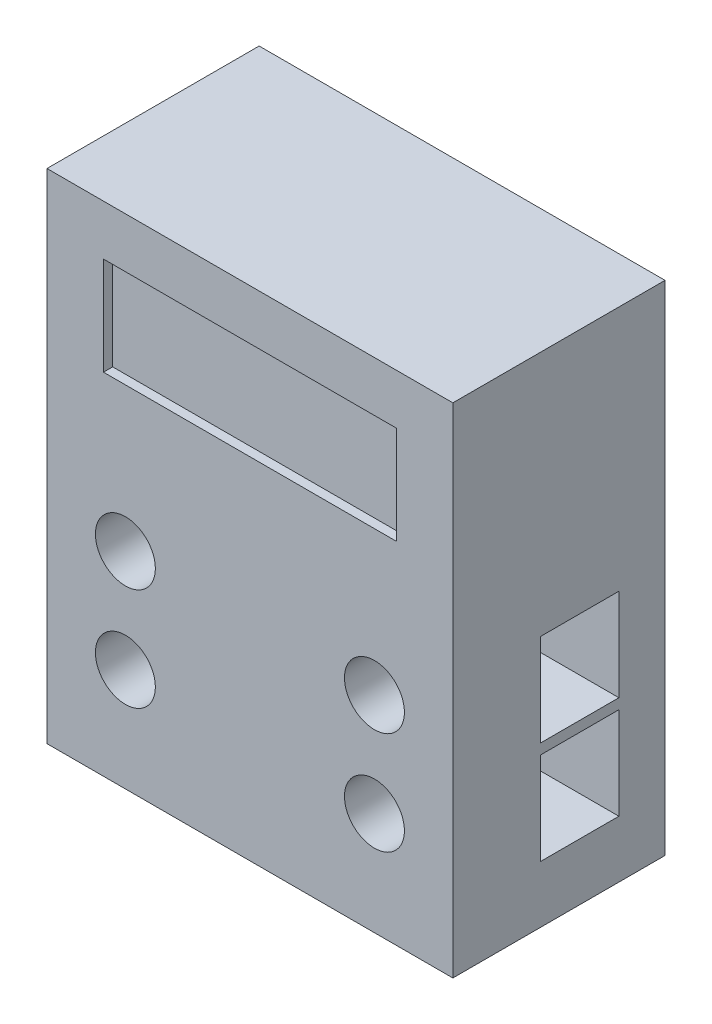
SolidWorks part; units mm, degrees
ref_plane "Front Plane" through (0, 0, 0) normal (0, 0, 1) x (1, 0, 0)
ref_plane "Top Plane" through (0, 0, 0) normal (0, 1, 0) x (1, 0, 0)
ref_plane "Right Plane" through (0, 0, 0) normal (1, 0, 0) x (0, 0, -1)
sketch "Sketch2" plane through (0, 0, 0) normal (0, 0, 1) x (1, 0, 0)
  line L0 (0, 32.5) -> (0, 0) construction
  line L1 (43.9999, -54) -> (-43.9999, -54)
  line L2 (43.9999, -54) -> (43.9999, 54)
  line L3 (43.9999, 54) -> (-43.9999, 54)
  line L4 (-43.9999, -54) -> (-43.9999, 54)
  line L5 (43.9999, -54) -> (-43.9999, 54) construction
  line L6 (43.9999, 54) -> (-43.9999, -54) construction
  line L9 (0, 0) -> (0, -20.5) construction
  line L10 (-31.75, 43.125) -> (31.75, 43.125)
  line L11 (-31.75, 43.125) -> (-31.75, 21.875)
  line L12 (-31.75, 21.875) -> (31.75, 21.875)
  line L13 (31.75, 43.125) -> (31.75, 21.875)
  line L14 (-31.75, 43.125) -> (31.75, 21.875) construction
  line L15 (-31.75, 21.875) -> (31.75, 43.125) construction
  line L16 (27, -31.625) -> (-27, -31.625)
  line L17 (27, -31.625) -> (27, -9.375)
  line L18 (27, -9.375) -> (-27, -9.375)
  line L19 (-27, -31.625) -> (-27, -9.375)
  line L20 (27, -31.625) -> (-27, -9.375) construction
  line L21 (27, -9.375) -> (-27, -31.625) construction
  circle A0 centre (-27, -9.375) radius 6.5
  circle A1 centre (27, -9.375) radius 6.5
  circle A2 centre (27, -31.625) radius 6.5
  circle A3 centre (-27, -31.625) radius 6.5
  point P0 (0, 0)
  point P5 (0, 32.5)
  point P8 (0, 0)
  point P26 (0, -20.5)
  dimension "D4" = 13
  dimension "D1" = 108
  dimension "D2" = 21.25
  dimension "D3" = 63.5
  dimension "D5" = 22.25
  dimension "D6" = 54
  dimension "D7" = 87.9997
  dimension "D8" = 32.5
  dimension "D9" = 20.5
extrude "Boss-Extrude1" add sketch "Sketch2" against normal blind 46 contours L4 L1 L2 L3 A3 L19 A0 L18 A1 L17 A2 L16 L10 L13 L12 L11 | A3 L16 A2 L17 A1 L18 A0 L19 region at (0, -1.6874, 0) region at (0, -20.5, 0)
sketch "Sketch3" plane through (0, 0, 0) normal (1, 0, 0) x (0, 0, -1)
  line L0 (46, -54) -> (0, -54) construction
  line L1 (46, 54) -> (0.0001, 54)
  line L2 (46, 54) -> (46, -54)
  line L3 (46, -54) -> (0.0001, -54)
  line L4 (0.0001, 54) -> (0.0001, -54)
  line L5 (46, 54) -> (0.0001, -54) construction
  line L6 (46, -54) -> (0.0001, 54) construction
  line L7 (46, -54) -> (46, 54) construction
  line L8 (23, -15.875) -> (23, -25.125) construction
  line L9 (30.5308, -2.875) -> (30.5308, -15.875) construction
  line L18 (34, 0.625) -> (34, -19.375)
  line L19 (34, -9.375) -> (27.5, -9.375) construction
  line L20 (36, -19.375) -> (34, -19.375)
  line L21 (36, 0.625) -> (36, -19.375)
  line L22 (36, 0.625) -> (34, 0.625)
  line L23 (34, -19.375) -> (34, 0.625)
  line L24 (19, 0.625) -> (34, 0.625)
  line L25 (19, -19.375) -> (19, 0.625)
  line L26 (19, -19.375) -> (34, -19.375)
  line L27 (46, -2.875) -> (0, -2.875) construction
  line L28 (0, -15.875) -> (46, -15.875) construction
  line L29 (46, -25.125) -> (0, -25.125) construction
  line L30 (0.0001, -20.5) -> (46, -20.5) construction
  line L31 (34, -31.625) -> (27.5, -31.625) construction
  line L32 (30.5308, -38.125) -> (30.5308, -25.125) construction
  line L33 (19, -21.625) -> (34, -21.625)
  line L34 (19, -21.625) -> (19, -41.625)
  line L35 (19, -41.625) -> (34, -41.625)
  line L36 (34, -21.625) -> (34, -41.625)
  line L37 (36, -41.625) -> (34, -41.625)
  line L38 (36, -41.625) -> (36, -21.625)
  line L39 (36, -21.625) -> (34, -21.625)
  line L40 (34, -41.625) -> (34, -21.625)
  arc A1 (34, -17.625) -> (34, -1.125) centre (35.9856, -9.375) cw
  arc A2 (34, -23.375) -> (34, -39.875) centre (35.9856, -31.625) ccw
  point P0 (23, 0)
  point P8 (30.5308, -9.375)
  point P18 (23, -15.875)
  point P19 (23, -20.5)
  point P48 (23, -41)
  point P49 (0, 0)
  dimension "D4" = 6.5
  dimension "D7" = 1.75
  dimension "D1" = 108
  dimension "D2" = 20
  dimension "D3" = 45.9999
  dimension "D5" = 2
  dimension "D6" = 15
  dimension "D8" = 10
sketch "Sketch4" plane through (0, 0, -46) normal (0, 0, -1) x (-1, 0, 0)
  line L1 (-31.75, 21.875) -> (31.75, 21.875)
  line L2 (-31.75, 21.875) -> (-31.75, 43.125)
  line L3 (-31.75, 43.125) -> (31.75, 43.125)
  line L4 (31.75, 21.875) -> (31.75, 43.125)
extrude "Boss-Extrude2" add sketch "Sketch4" against normal offset from surface (44 mm away) 2 up to face at (-20.5, -9.375, 0)
sketch "Sketch5" plane through (0, 0, -46) normal (0, 0, -1) x (-1, 0, 0)
  circle A0 centre (-27, -9.375) radius 6.5
  circle A1 centre (-27, -31.625) radius 6.5
  circle A2 centre (27, -31.625) radius 6.5
  circle A3 centre (27, -9.375) radius 6.5
  circle A5 centre (-27, -9.375) radius 6.5 construction
extrude "Boss-Extrude3" add sketch "Sketch5" against normal blind 10
extrude "Cut-Extrude1" cut sketch "Sketch3" against normal blind 27 from surface contours L18 A1 L24 L25 L26 | L21 L22 L18 L23 L20 | A2 L36 L33 L34 L35 | L40 A2 | L38 L39 L36 L40 L37 | A1 L23 region at (0, -9.375, -35) region at (0, -9.375, -24.7667) region at (0, -9.375, -31.2897) region at (0, -31.625, -24.7667) region at (0, -31.625, -35) region at (0, -31.625, -31.2897) starting at face at (43.9999, 0, -23)
extrude "Cut-Extrude2" cut sketch "Sketch3<3>" along normal blind 27 from surface contours L18 A1 L24 L25 L26 | A1 L23 | L21 L22 L18 L23 L20 | L38 L39 L36 L40 L37 | L40 A2 | A2 L36 L33 L34 L35 region at (0, -9.375, -35) region at (0, -9.375, -24.7667) region at (0, -9.375, -31.2897) region at (0, -31.625, -24.7667) region at (0, -31.625, -35) region at (0, -31.625, -31.2897) starting at face at (-43.9999, 0, -23)
sketch "Sketch3<3>" plane through (0, 0, 0) normal (1, 0, 0) x (0, 0, -1) same geometry as "Sketch3"
